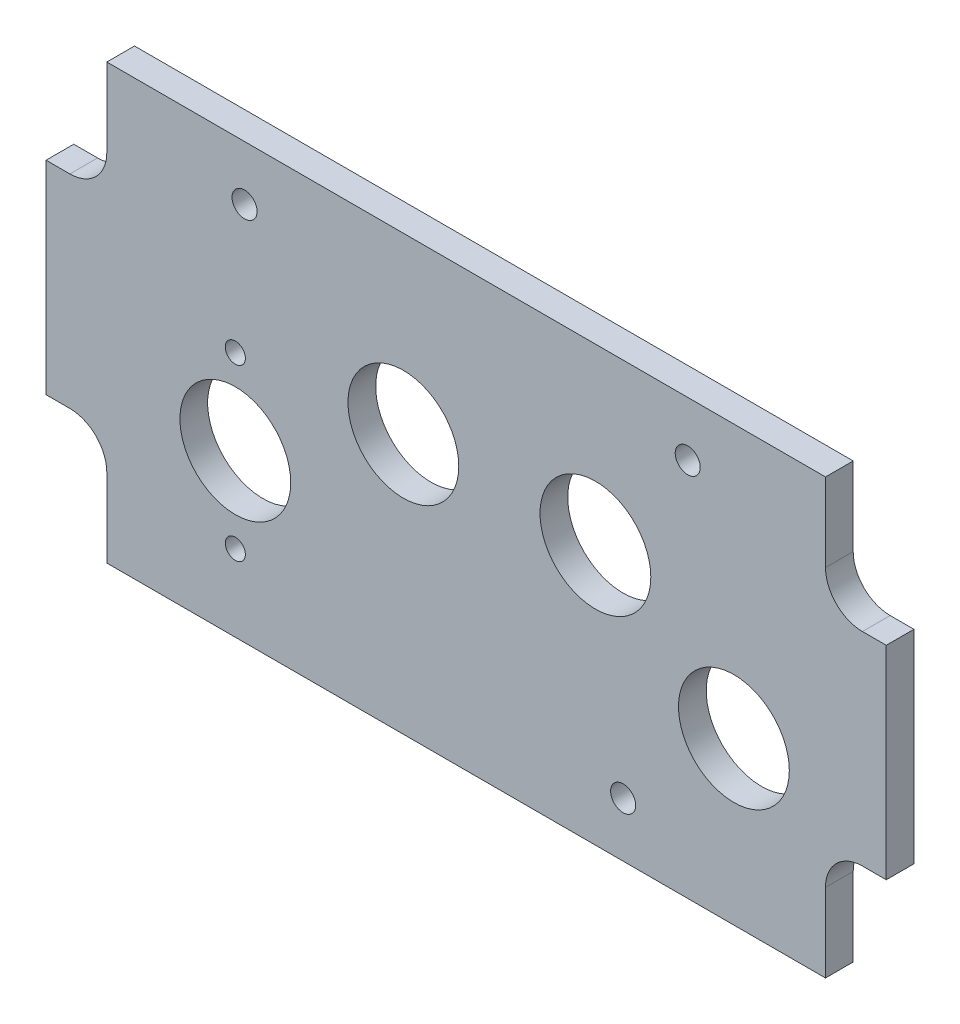
SolidWorks part; units mm, degrees
ref_plane "Front Plane" through (0, 0, 0) normal (0, 0, 1) x (1, 0, 0)
ref_plane "Top Plane" through (0, 0, 0) normal (0, 1, 0) x (1, 0, 0)
ref_plane "Right Plane" through (0, 0, 0) normal (1, 0, 0) x (0, 0, -1)
sketch "Sketch1" plane through (0, 0, 0) normal (0, 0, 1) x (1, 0, 0)
  line L12 (11.2395, 14.2875) -> (11.2395, 0.7938)
  line L13 (11.2395, 0.7938) -> (134.8105, 0.7938)
  line L14 (134.8105, 0.7938) -> (134.8105, 14.2875)
  line L15 (141.1605, 20.6375) -> (145.2562, 20.6375)
  line L16 (145.2562, 20.6375) -> (145.2562, 55.5625)
  line L17 (145.2562, 55.5625) -> (141.1605, 55.5625)
  line L18 (134.8105, 61.9125) -> (134.8105, 75.4062)
  line L19 (134.8105, 75.4062) -> (11.2395, 75.4062)
  line L20 (11.2395, 75.4062) -> (11.2395, 61.9125)
  line L21 (4.8895, 55.5625) -> (0.7937, 55.5625)
  line L22 (0.7937, 55.5625) -> (0.7937, 20.6375)
  line L23 (0.7937, 20.6375) -> (4.8895, 20.6375)
  line L24 (11.2395, 14.2875) -> (11.2395, 0.7938)
  line L25 (11.2395, 0.7938) -> (134.8105, 0.7938)
  line L26 (134.8105, 0.7938) -> (134.8105, 14.2875)
  line L27 (141.1605, 20.6375) -> (145.2562, 20.6375)
  line L28 (145.2562, 20.6375) -> (145.2562, 55.5625)
  line L29 (145.2562, 55.5625) -> (141.1605, 55.5625)
  line L30 (134.8105, 61.9125) -> (134.8105, 75.4062)
  line L31 (134.8105, 75.4062) -> (11.2395, 75.4062)
  line L32 (11.2395, 75.4062) -> (11.2395, 61.9125)
  line L33 (4.8895, 55.5625) -> (0.7937, 55.5625)
  line L34 (0.7937, 55.5625) -> (0.7937, 20.6375)
  line L35 (0.7937, 20.6375) -> (4.8895, 20.6375)
  arc A4 (11.2395, 14.2875) -> (4.8895, 20.6375) centre (4.8895, 14.2875) ccw
  arc A5 (141.1605, 20.6375) -> (134.8105, 14.2875) centre (141.1605, 14.2875) ccw
  arc A6 (134.8105, 61.9125) -> (141.1605, 55.5625) centre (141.1605, 61.9125) ccw
  arc A7 (4.8895, 55.5625) -> (11.2395, 61.9125) centre (4.8895, 61.9125) ccw
  arc A8 (11.2395, 14.2875) -> (4.8895, 20.6375) centre (4.8895, 14.2875) ccw
  arc A9 (141.1605, 20.6375) -> (134.8105, 14.2875) centre (141.1605, 14.2875) ccw
  arc A10 (134.8105, 61.9125) -> (141.1605, 55.5625) centre (141.1605, 61.9125) ccw
  arc A11 (4.8895, 55.5625) -> (11.2395, 61.9125) centre (4.8895, 61.9125) ccw
  dimension "D1" = 0
extrude "Boss-Extrude1" add sketch "Sketch1" along normal blind 4.7625
hole_wizard "#4 Clearance Hole1" positions "Sketch3" profile "Sketch2" hole size "#4" standard "ANSI Inch" end condition through all
sketch "Sketch3" plane through (0, 0, 4.7625) normal (0, 0, 1) x (1, 0, 0)
  point P0 (33.3375, 43.18)
  point P3 (33.3375, 13.97)
sketch "Sketch2" plane through (33.3375, 43.18, 4.7625) normal (1, 0, 0) x (0, -1, 0)
  line L0 (0, 0) -> (0, 4.7625)
  line L1 (0, 4.7625) -> (1.7272, 4.7625)
  line L2 (1.7272, 4.7625) -> (1.7272, 0)
  line L5 (1.7272, 0) -> (0, 0)
  line L11 (0, -6.35) -> (0, 107.95) construction
  dimension "Thru Hole Dia." = 3.4544
  dimension "Thru Hole Depth" = 4.7625
hole_wizard "#6 Clearance Hole1" positions "Sketch5" profile "Sketch4" hole size "#6" standard "ANSI Inch" end condition through all
sketch "Sketch5" plane through (0, 0, 4.7625) normal (0, 0, 1) x (1, 0, 0)
  point P0 (34.925, 66.04)
  point P3 (111.125, 66.04)
  point P6 (100.015, 10.16)
sketch "Sketch4" plane through (34.925, 66.04, 4.7625) normal (1, 0, 0) x (0, -1, 0)
  line L0 (0, 0) -> (0, 4.7625)
  line L1 (0, 4.7625) -> (2.1526, 4.7625)
  line L2 (2.1526, 4.7625) -> (2.1526, 0)
  line L5 (2.1526, 0) -> (0, 0)
  line L11 (0, -6.35) -> (0, 107.95) construction
  dimension "Thru Hole Dia." = 4.3053
  dimension "Thru Hole Depth" = 4.7625
hole_wizard "3/4 (0.75) Diameter Hole1" positions "Sketch7" profile "Sketch6" hole size "3/4" standard "ANSI Inch" end condition through all
sketch "Sketch7" plane through (0, 0, 4.7625) normal (0, 0, 1) x (1, 0, 0)
  point P0 (119.0625, 28.575)
  point P3 (95.25, 45.466)
  point P6 (62.23, 45.466)
  point P9 (33.3375, 28.575)
sketch "Sketch6" plane through (119.0625, 28.575, 4.7625) normal (1, 0, 0) x (0, -1, 0)
  line L0 (0, 0) -> (0, 4.7625)
  line L1 (0, 4.7625) -> (9.525, 4.7625)
  line L2 (9.525, 4.7625) -> (9.525, 0)
  line L5 (9.525, 0) -> (0, 0)
  line L11 (0, -6.35) -> (0, 107.95) construction
  dimension "Thru Hole Dia." = 19.05
  dimension "Thru Hole Depth" = 4.7625
